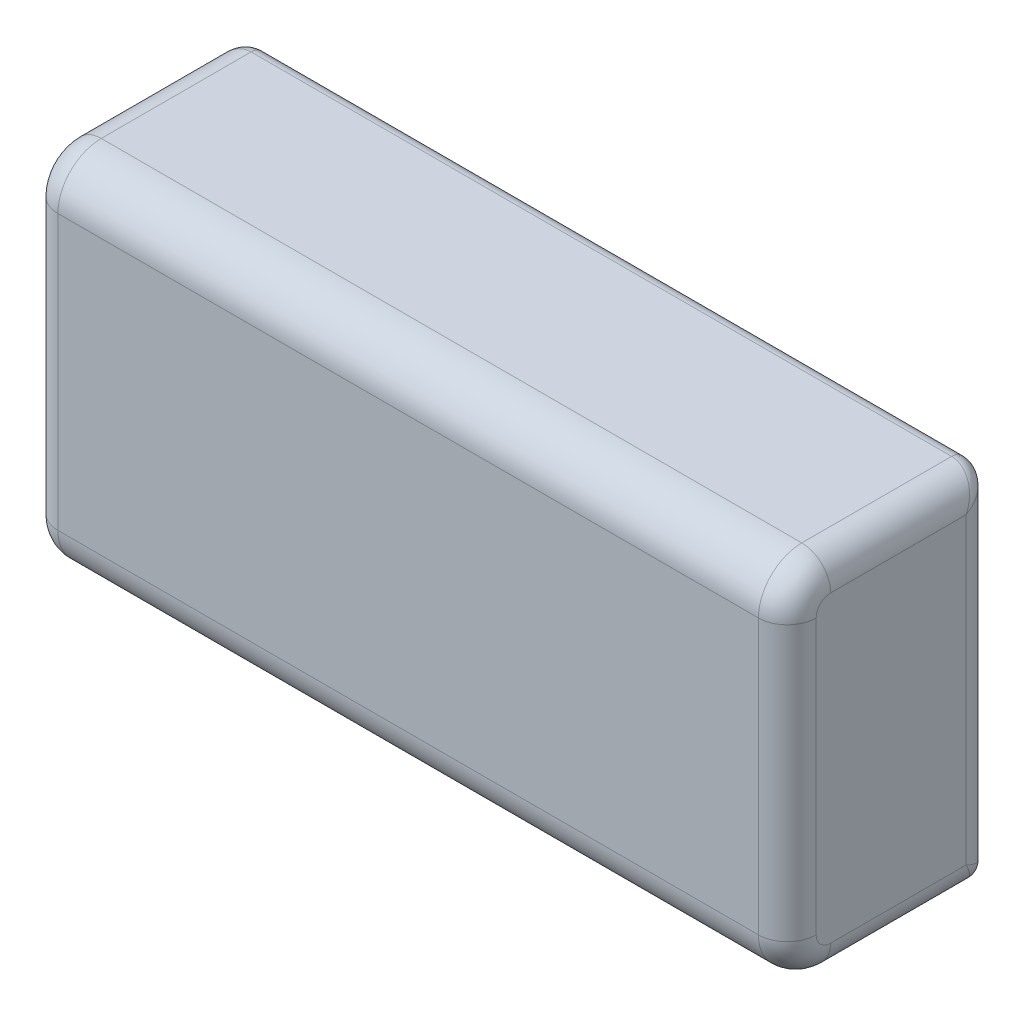
SolidWorks part; units mm, degrees
material "Polyurethane Foam Rigid"
ref_plane "Front Plane" through (0, 0, 0) normal (0, 0, 1) x (1, 0, 0)
ref_plane "Top Plane" through (0, 0, 0) normal (0, 1, 0) x (1, 0, 0)
ref_plane "Right Plane" through (0, 0, 0) normal (1, 0, 0) x (0, 0, -1)
sketch "Sketch1" plane through (0, 0, 0) normal (1, 0, 0) x (0, 0, -1)
  line L0 (0, 63.5) -> (-57.785, 63.5)
  line L1 (0, -63.5) -> (-9.525, -63.5) construction
  line L2 (0, -63.5) -> (0, 63.5)
  line L3 (0, 63.5) -> (-9.525, 63.5) construction
  line L4 (-9.525, -63.5) -> (-9.525, 63.5) construction
  line L6 (-73.025, 48.26) -> (-73.025, -48.26)
  line L8 (-57.785, -63.5) -> (0, -63.5)
  circle A0 centre (-41.275, 31.75) radius 31.75 construction
  circle A1 centre (-41.275, -31.75) radius 31.75 construction
  arc A2 (-73.025, -48.26) -> (-57.785, -63.5) centre (-57.785, -48.26) ccw
  arc A3 (-73.025, 48.26) -> (-57.785, 63.5) centre (-57.785, 48.26) cw
  dimension "D3" = 15.24
  dimension "D4" = 15.24
  dimension "D1" = 9.525
  dimension "D2" = 127
extrude "Boss-Extrude1" add sketch "Sketch1" along normal blind 266.7
fillet "Fillet1" radius 10.16 12 edges at (0, 0, 0) (0, 63.5, 28.8925) (0, 59.0363, 68.5613) (0, 0, 73.025) (0, -59.0363, 68.5613) (0, -63.5, 28.8925) (266.7, -59.0363, 68.5613) (266.7, 0, 73.025) (266.7, 59.0363, 68.5613) (266.7, 63.5, 28.8925) (266.7, 0, 0) (266.7, -63.5, 28.8925)
fillet "Fillet2" radius 5.08 6 edges at (263.7242, 60.5242, 2.9758) (2.9758, 60.5242, 2.9758) (263.7242, -60.5242, 2.9758) (2.9758, -60.5242, 2.9758) (133.35, 63.5, 0) (133.35, -63.5, 0)
